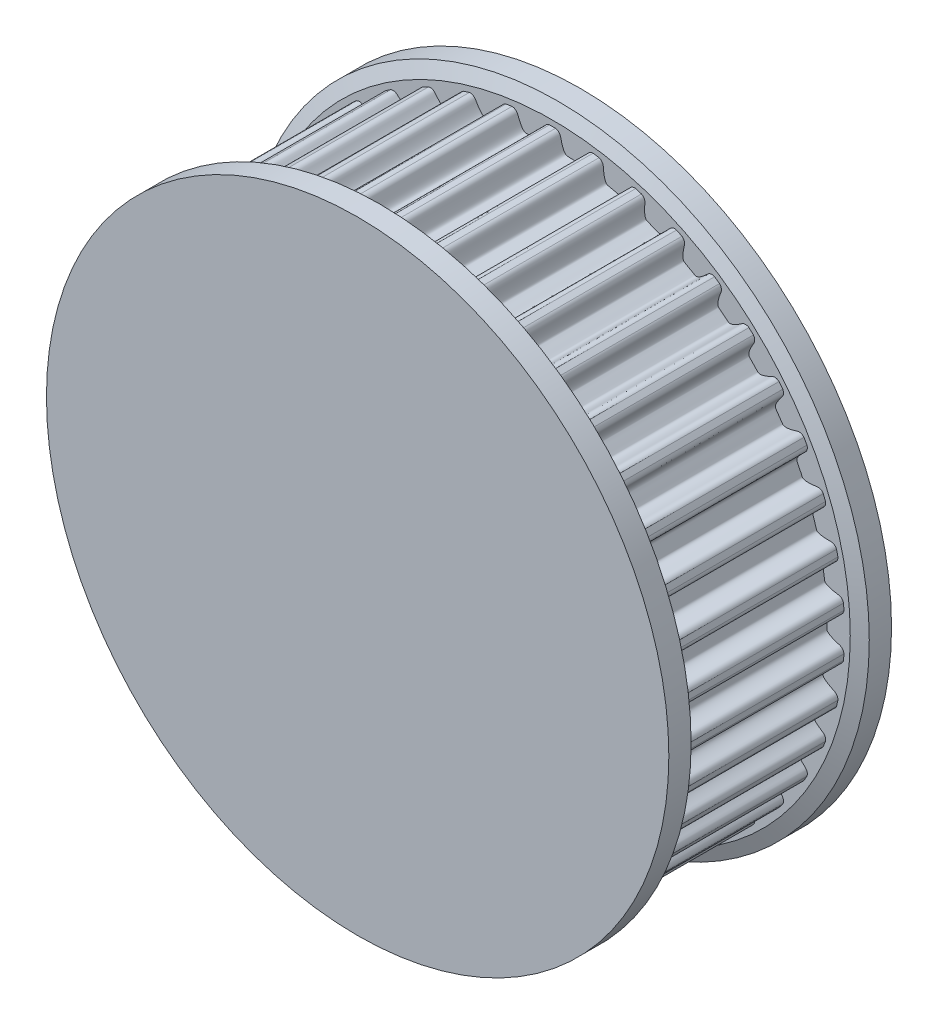
SolidWorks part; units mm, degrees
ref_plane "Front Plane" through (0, 0, 0) normal (0, 0, 1) x (1, 0, 0)
ref_plane "Top Plane" through (0, 0, 0) normal (0, 1, 0) x (1, 0, 0)
ref_plane "Right Plane" through (0, 0, 0) normal (1, 0, 0) x (0, 0, -1)
ref_axis "Axis1" through (0, 0, 55) along (0, 0, -1)
sketch "SketchRevolveGearBelt01" plane through (0, 0, 0) normal (1, 0, 0) x (0, 0, -1)
  line L0 (0, 0) -> (1, 0) construction
  line L1 (5.274, 0) -> (5.274, 11.869)
  line L2 (5.274, 11.869) -> (4.512, 11.869)
  line L3 (4.512, 11.869) -> (4.512, 13.2174)
  line L4 (4.512, 13.2174) -> (4.7696, 13.8394)
  line L5 (4.7696, 13.8394) -> (4.0656, 14.131)
  line L6 (4.0656, 14.131) -> (3.75, 13.369)
  line L7 (3.75, 13.369) -> (3.75, 13.1129)
  line L8 (3.75, 13.1129) -> (-3.75, 13.1129)
  line L9 (-3.75, 13.1129) -> (-3.75, 13.369)
  line L10 (-3.75, 13.369) -> (-4.0656, 14.131)
  line L11 (-4.0656, 14.131) -> (-4.7696, 13.8394)
  line L12 (-4.7696, 13.8394) -> (-4.512, 13.2174)
  line L13 (-4.512, 13.2174) -> (-4.512, 11.869)
  line L14 (-4.512, 11.869) -> (-5.274, 11.869)
  line L15 (-5.274, 11.869) -> (-5.274, 0)
  line L16 (-5.274, 0) -> (5.274, 0)
  dimension "GearBeltSide1" = 5.274
  dimension "GearBeltFlange1OutsideWidth" = 4.512
  dimension "GearBeltFlange1OutsideLength" = 1.3484
  dimension "GearBeltFlange1X" = 0.2576
  dimension "GearBeltFlange1Y" = 0.622
  dimension "GearBeltFlangeThickness" = 0.762
  dimension "GearBeltToothWidth1" = 3.75
  dimension "GearBeltFlangeInside" = 0.2561
  dimension "GearBeltOutsideDiameter" = 13.1129
  dimension "GearBeltToothWidth2" = 3.75
  dimension "GearBeltFlange2X" = 0.2576
  dimension "GearBeltFlange2OutsideWidth" = 4.512
revolve "GearBelt01" add sketch "SketchRevolveGearBelt01" angle 360 about L0
sketch "SketchToothGearBelt01" plane through (0, 0, 0) normal (0, 0, 1) x (1, 0, 0)
  arc A0 (13.0862, 0.8615) -> (13.0862, -0.8615) centre (0, 0) cw
  spline S0 degree 3 poles (13.0862, -0.8615) (13.0862, -0.8442) (13.0837, -0.8183) (13.0754, -0.7847) (13.0668, -0.7602) (13.0558, -0.7366) (13.0426, -0.7143) (13.0273, -0.6933) (13.01, -0.6739) (12.9909, -0.6563) (12.9702, -0.6406) (12.9481, -0.6271) (12.9247, -0.6156) (12.8852, -0.6016) (12.8348, -0.5863) (12.7752, -0.5675) (12.7227, -0.5498) (12.6735, -0.5322) (12.6274, -0.5145) (12.5844, -0.4969) (12.5447, -0.4793) (12.5081, -0.4616) (12.4747, -0.444) (12.4444, -0.4264) (12.4173, -0.4087) (12.3934, -0.3911) (12.3726, -0.3735) (12.355, -0.3558) (12.3405, -0.3381) (12.3292, -0.3203) (12.3211, -0.3025) (12.3161, -0.2846) (12.3139, -0.2503) (12.3171, -0.2) (12.3172, -0.1333) (12.318, -0.0667) (12.3181, 0) (12.318, 0.0667) (12.3172, 0.1333) (12.3171, 0.2) (12.3139, 0.2503) (12.3161, 0.2846) (12.3211, 0.3025) (12.3292, 0.3203) (12.3405, 0.3381) (12.355, 0.3558) (12.3726, 0.3735) (12.3934, 0.3911) (12.4173, 0.4087) (12.4444, 0.4264) (12.4747, 0.444) (12.5081, 0.4616) (12.5447, 0.4793) (12.5844, 0.4969) (12.6274, 0.5145) (12.6735, 0.5322) (12.7227, 0.5498) (12.7752, 0.5675) (12.8348, 0.5863) (12.8852, 0.6016) (12.9247, 0.6156) (12.9481, 0.6271) (12.9702, 0.6406) (12.9909, 0.6563) (13.01, 0.6739) (13.0273, 0.6933) (13.0426, 0.7143) (13.0558, 0.7366) (13.0668, 0.7602) (13.0754, 0.7847) (13.0837, 0.8183) (13.0862, 0.8442) (13.0862, 0.8615) knots 0 0 0 0 0.019806 0.029709 0.039613 0.049516 0.059419 0.069322 0.079225 0.089128 0.099031 0.108935 0.118838 0.128741 0.156934 0.179221 0.200353 0.22034 0.239188 0.256909 0.273513 0.289016 0.303437 0.316796 0.329124 0.340455 0.350836 0.360328 0.369009 0.376982 0.38438 0.391369 0.398144 0.423627 0.449084 0.474542 0.5 0.525458 0.550916 0.576373 0.601856 0.608631 0.61562 0.623018 0.630991 0.639672 0.649164 0.659545 0.670876 0.683204 0.696563 0.710984 0.726487 0.743091 0.760812 0.77966 0.799647 0.820779 0.843066 0.871259 0.881162 0.891065 0.900969 0.910872 0.920775 0.930678 0.940581 0.950484 0.960387 0.970291 0.980194 1 1 1 1
extrude "ToothExtrudeCutGearBelt01" cut sketch "SketchToothGearBelt01" against normal blind 3.75 and the other way blind 3.75
pattern_circular "PatternGearBelt01" count 42 every 8.571 about axis through (0, 0, 55) along (0, 0, -1) of "ToothExtrudeCutGearBelt01"
sketch "BoreRevolveSketch" plane through (0, 0, 0) normal (1, 0, 0) x (0, 0, -1)
  line L0 (0, 0) -> (1, 0) construction
  line L1 (-5.274, 0) -> (5.274, 0)
  line L2 (5.274, 0) -> (5.274, 5)
  line L3 (5.274, 5) -> (-5.274, 5)
  line L4 (-5.274, 5) -> (-5.274, 0)
  dimension "BoreSide1" = 5.274
  dimension "TaperSide1" = 5
  dimension "BoreSide2" = 5.274
  dimension "TaperSide2" = 5
revolve "BoreRevolveCut" cut sketch "BoreRevolveSketch" angle 360 about L0
sketch "AuxiliarySketchGearBelt01" plane through (0, 0, 0) normal (0, 0, 1) x (1, 0, 0)
  circle A0 centre (0, 0) radius 13.369 construction
  dimension "PitchDiameter" = 26.738
sketch "Sketch1" plane through (0, 0, 0) normal (0, 1, 0) x (1, 0, 0)
  line L0 (0, 0) -> (26.4041, 0) construction
  line L1 (-100.3329, 38.1802) -> (30.787, 38.1802)
  line L2 (-100.3329, 38.1802) -> (-100.3329, 4)
  line L3 (-100.3329, 4) -> (30.787, 4)
  line L4 (30.787, 38.1802) -> (30.787, 4)
  line L5 (-100.3329, 38.1802) -> (30.787, 4) construction
  line L6 (-100.3329, 4) -> (30.787, 38.1802) construction
  line L7 (-13.369, 0) -> (13.369, 0) construction
  line L8 (-100.3329, -38.1802) -> (-100.3329, -4)
  line L9 (-100.3329, -38.1802) -> (30.787, -38.1802)
  line L10 (30.787, -38.1802) -> (30.787, -4)
  line L11 (-100.3329, -4) -> (30.787, -4)
  point P0 (-34.773, 21.0901)
  dimension "D1" = 4
extrude "Cut-Extrude1" cut sketch "Sketch1" against normal through all both and the other way through all
sketch "Sketch2" plane through (0, 0, 4) normal (0, 0, 1) x (1, 0, 0)
  circle A0 centre (0, 0) radius 6.2843
extrude "Boss-Extrude1" add sketch "Sketch2" against normal up to surface (8 mm away) up to face at (5, 0, -4)
sketch "Sketch3" plane through (0, 0, 4) normal (0, 0, 1) x (1, 0, 0)
  circle A1 centre (0, 0) radius 13.9726
  circle A2 centre (0, 0) radius 13.9726
  dimension "D1" = 0
extrude "Boss-Extrude2" add sketch "Sketch3" along normal blind 1
sketch "Sketch4" plane through (0, 0, -4) normal (0, 0, -1) x (-1, 0, 0)
  circle A1 centre (0, 0) radius 13.9726
  circle A2 centre (0, 0) radius 13.9726
  dimension "D1" = 0
extrude "Boss-Extrude3" add sketch "Sketch4" along normal blind 1
